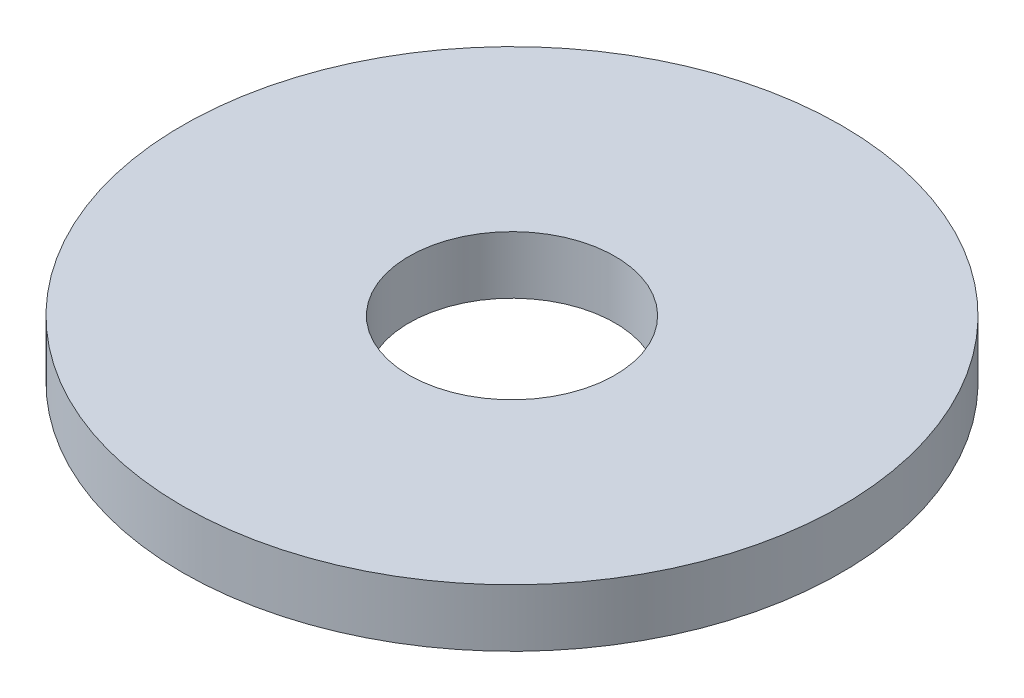
SolidWorks part; units mm, degrees
ref_plane "Front Plane" through (0, 0, 0) normal (0, 0, 1) x (1, 0, 0)
ref_plane "Top Plane" through (0, 0, 0) normal (0, 1, 0) x (1, 0, 0)
ref_plane "Right Plane" through (0, 0, 0) normal (1, 0, 0) x (0, 0, -1)
sketch "Sketch1" plane through (0, 0, 0) normal (0, 1, 0) x (1, 0, 0)
  circle A0 centre (0, 0) radius 80
  dimension "FLANGE_OD" = 160
extrude "Boss-Extrude1" add sketch "Sketch1" along normal blind 14
sketch "Sketch2" plane through (0, 0, 0) normal (0, 1, 0) x (1, 0, 0)
  circle A0 centre (0, 0) radius 25
  dimension "BORE_D" = 50
extrude "Cut-Extrude1" cut sketch "Sketch2" along normal through all
sketch "Sketch3" plane through (0, 14, 0) normal (0, 1, 0) x (1, 0, 0)
  circle A0 centre (0, 0) radius 19.4521 construction
  circle A1 centre (-19.4521, 0) radius 3.9279
  dimension "BOLT_D" = 7.8557
  dimension "BOLT_PCD" = 38.9042
extrude "Cut-Extrude2" cut sketch "Sketch3" against normal blind 11.5521 rebuild error yes
pattern_circular "CirPattern1" count 8 over 360 rebuild error yes
